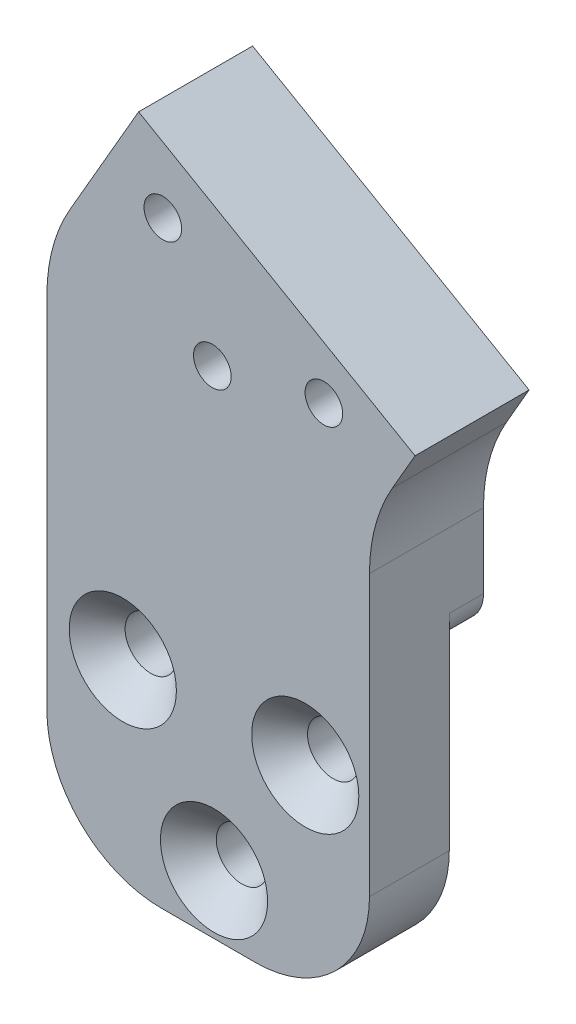
SolidWorks part; units mm, degrees
ref_plane "Front Plane" through (0, 0, 0) normal (0, 0, 1) x (1, 0, 0)
ref_plane "Top Plane" through (0, 0, 0) normal (0, 1, 0) x (1, 0, 0)
ref_plane "Right Plane" through (0, 0, 0) normal (1, 0, 0) x (0, 0, -1)
sketch "Sketch1" plane through (0, 0, 0) normal (0, 0, 1) x (1, 0, 0)
  line L5 (-14.6579, 119.617) -> (13.6331, 119.617)
  line L12 (13.6331, 119.617) -> (13.6331, 139.617)
  line L15 (-14.6579, 119.617) -> (-14.6579, 139.617)
  line L18 (-14.6579, 139.617) -> (-14.6579, 158.1769)
  line L20 (13.6331, 158.1769) -> (13.6331, 139.617)
  line L21 (-14.6579, 158.1769) -> (-14.6579, 165.1755)
  line L22 (-10.6157, 172.1769) -> (-14.6579, 165.1755)
  line L23 (-6.6157, 179.1051) -> (-10.6157, 172.1769)
  line L24 (17.6331, 165.1051) -> (13.6331, 158.1769)
  line L25 (-6.6157, 179.1051) -> (17.6331, 165.1051)
extrude "Boss-Extrude1" add sketch "Sketch1" along normal blind 9 and the other way blind 1
sketch "Sketch3" plane through (0, 0, -1) normal (0, 0, -1) x (-1, 0, 0)
  line L16 (-15, 144.2481) -> (-15, 114.7859)
  line L17 (-15, 114.7859) -> (15, 114.7859)
  line L18 (15, 114.7859) -> (15, 144.2481)
  arc A2 (15, 144.2481) -> (-15, 144.2481) centre (0, -5) ccw
extrude "Cut-Extrude1" cut sketch "Sketch3" against normal blind 3
sketch "Sketch7" plane through (0, 0, 9) normal (0, 0, -1) x (-1, 0, 0)
  line L2 (0, 124.7859) -> (0, 136.7859)
  line L3 (0, 136.7859) -> (8, 136.7859)
  line L4 (0, 136.7859) -> (-8, 136.7859)
  circle A0 centre (8, 136.7859) radius 2
  circle A1 centre (0, 124.7859) radius 2
  circle A2 centre (-8, 136.7859) radius 2
hole_wizard "CSK for M4 Countersunk Flat Head Screw2" positions "Sketch11" profile "Sketch10" countersink size "M4" standard "ISO" end condition through all
sketch "Sketch11" plane through (0, 0, 9) normal (0, 0, 1) x (1, 0, 0)
  point P0 (0, 0)
  point P1 (8, 136.7859)
  point P4 (-8, 136.7859)
  point P7 (0, 124.7859)
sketch "Sketch10" plane through (0, 0, 9) normal (1, 0, 0) x (0, -1, 0)
  line L0 (0, 0) -> (0, 10)
  line L1 (0, 10) -> (2.25, 10)
  line L2 (2.25, 10) -> (2.25, 2.45)
  line L3 (2.25, 2.45) -> (4.7, 0)
  line L5 (4.7, 0) -> (0, 0)
  line L6 (-2.25, 2.45) -> (-4.7, 0) construction
  line L11 (0, -6.35) -> (0, 107.95) construction
  dimension "Thru Hole Dia." = 4.5
  dimension "Thru Hole Depth" = 10
  dimension "Near C'Sink Dia." = 9.4
  dimension "Near C'Sink Angle" = 90
fillet "Fillet1" radius 15 2 edges at (13.6331, 158.1769, 4) (-14.6579, 165.1755, 4)
fillet "Fillet2" radius 10 2 edges at (-14.6579, 119.617, 5.5) (13.6331, 119.617, 5.5)
fillet "Fillet3" radius 3 2 edges at (13.6331, 144.3792, 0.5) (-14.6579, 144.2821, 0.5)
sketch "Sketch12" plane through (0, 0, -1) normal (0, 0, -1) x (-1, 0, 0)
  circle A0 centre (4.4913, 172.1051) radius 1.65
  circle A1 centre (-9.6331, 165.1051) radius 1.65
  circle A2 centre (0.1468, 163.0385) radius 1.65
extrude "Cut-Extrude2" cut sketch "Sketch12" against normal through all
